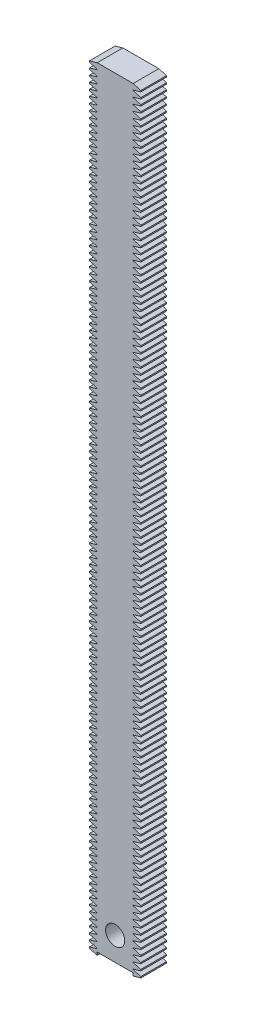
SolidWorks part; units mm, degrees
ref_plane "Front Plane" through (0, 0, 0) normal (0, 0, 1) x (1, 0, 0)
ref_plane "Top Plane" through (0, 0, 0) normal (0, 1, 0) x (1, 0, 0)
ref_plane "Right Plane" through (0, 0, 0) normal (1, 0, 0) x (0, 0, -1)
sketch "Sketch1" plane through (0, 0, 0) normal (0, 1, 0) x (1, 0, 0)
  line L1 (-7, -5) -> (7, -5)
  line L2 (-7, -5) -> (-7, 5)
  line L3 (-7, 5) -> (7, 5)
  line L4 (7, -5) -> (7, 5)
  line L5 (-7, -5) -> (7, 5) construction
  line L6 (-7, 5) -> (7, -5) construction
  point P0 (0, 0)
extrude "Boss-Extrude1" add sketch "Sketch1" along normal blind 300
sketch "Sketch2" plane through (0, 0, 5) normal (0, 0, 1) x (1, 0, 0)
  line L0 (7, 300) -> (10, 299.1444)
  line L1 (10, 299.1444) -> (10, 298.6444)
  line L2 (10, 298.8944) -> (7, 298.8944) construction
  line L3 (7, 300) -> (7, 0) construction
  line L4 (7, 297.7887) -> (10, 298.6444)
  line L5 (0, -700) -> (0, 49300) construction
  line L6 (-7, 300) -> (7, 300) construction
  line L7 (-10, 298.8944) -> (-7, 298.8944) construction
  line L8 (-7, 297.7887) -> (-10, 298.6444)
  line L9 (-10, 299.1444) -> (-10, 298.6444)
  line L10 (-7, 300) -> (-10, 299.1444)
  line L11 (-7, 300) -> (-7, 297.7887)
  line L12 (7, 300) -> (7, 297.7887)
  point P9 (10, 298.8944)
  point P15 (0, 300)
  dimension "D1" = 3
extrude "Boss-Extrude2" add sketch "Sketch2" against normal up to surface (10 mm away) up to face at (0, 150, -5)
pattern_linear "LPattern1" count 126 spacing 2.3912 along (0, -1, 0) of "Boss-Extrude2"
sketch "Sketch3" plane through (0, 0, -5) normal (0, 0, -1) x (-1, 0, 0)
  circle A0 centre (0, 9.1292) radius 3.7268
extrude "Cut-Extrude1" cut sketch "Sketch3" against normal through all
